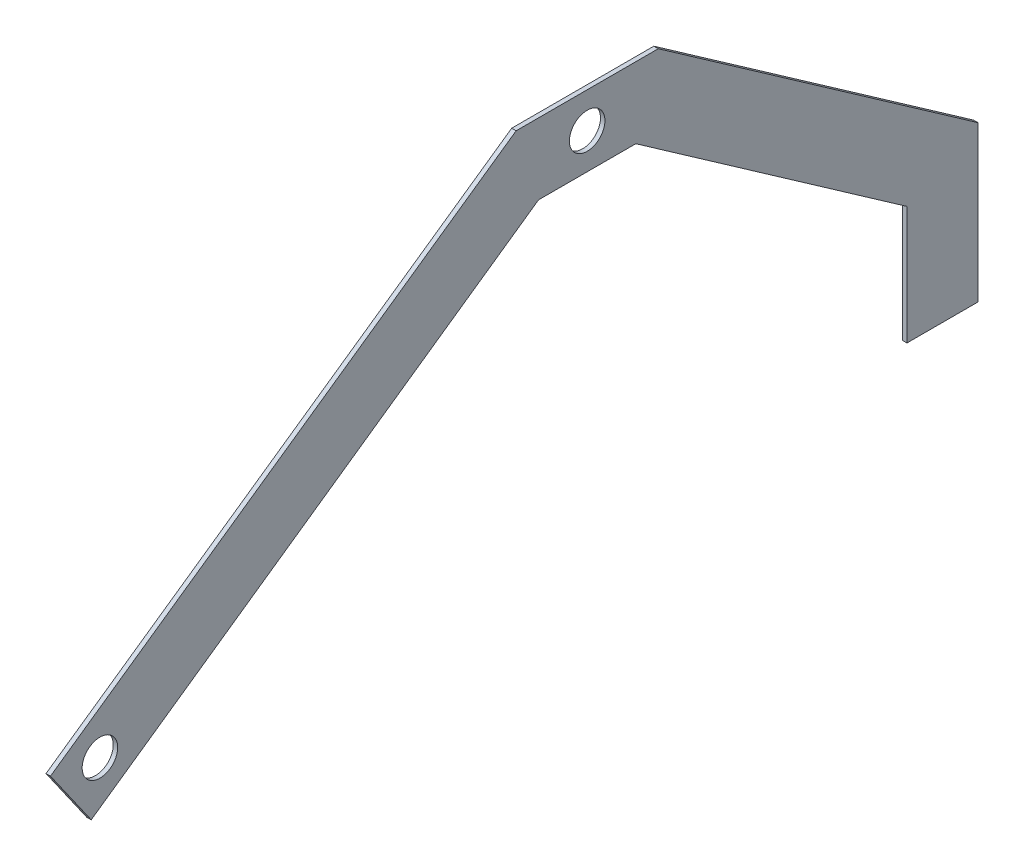
SolidWorks part; units mm, degrees
material "6063-O"
ref_plane "Front" through (0, 0, 0) normal (0, 0, 1) x (1, 0, 0)
ref_plane "Top" through (0, 0, 0) normal (0, 1, 0) x (1, 0, 0)
ref_plane "Right" through (0, 0, 0) normal (1, 0, 0) x (0, 0, -1)
sketch "Sketch1" plane through (0, 0, 0) normal (1, 0, 0) x (0, 0, -1)
  line L0 (-50.8, 25.4) -> (50.8, 25.4)
  line L3 (228.6, -161.1122) -> (34.7828, -25.4)
  line L4 (34.7828, -25.4) -> (-34.7828, -25.4)
  line L5 (-34.7828, -25.4) -> (-354.5657, -249.3144)
  line L6 (-354.5657, -249.3144) -> (-383.7034, -207.7015)
  line L7 (-383.7034, -207.7015) -> (-50.8, 25.4)
  line L8 (0, 25.4) -> (0, -25.4) construction
  line L9 (-278.5961, -165.1122) -> (-41236.1091, -28843.8715) construction
  line L13 (518.6127, -213.9391) -> (-49481.3873, -213.9391) construction
  line L14 (-147.7421, -347.18) -> (49852.2579, -347.18) construction
  line L15 (279.4, -134.6674) -> (279.4, -493.3391)
  line L16 (279.4, -493.3391) -> (228.6, -493.3391)
  line L17 (228.6, -493.3391) -> (228.6, -161.1122)
  line L18 (50.8, 25.4) -> (279.4, -134.6674)
  circle A0 centre (-348.3281, -213.9391) radius 12.7
  circle A1 centre (0, 0) radius 12.7
  point P10 (0, 0)
  point P16 (-369.1345, -228.5079)
  point P24 (254, -493.3391)
  dimension "D8" = 25.4
  dimension "D1" = 50.8
  dimension "D2" = 50.8
  dimension "D3" = 254
  dimension "D4" = 279.4
  dimension "D5" = 406.4
  dimension "D6" = 145
  dimension "D7" = 101.6
  dimension "D9" = 25.4
  dimension "D10" = 50.8
  dimension "D11" = 347.18
  dimension "D13" = 50.8
extrude "Boss-Extrude1" add sketch "Sketch1" along normal blind 3.175
sketch "Sketch3" plane through (3.175, 0, 0) normal (1, 0, 0) x (0, 0, -1)
  line L0 (254, -493.3391) -> (254, -116.8822) construction
  line L1 (228.6, -493.3391) -> (279.4, -493.3391) construction
  line L2 (279.4, -134.6674) -> (50.8, 25.4) construction
  circle A0 centre (254, -467.9391) radius 12.7
  dimension "D1" = 25.4
  dimension "D2" = 25.4
extrude "Cut-Extrude2" cut sketch "Sketch3" against normal through all
sketch "Sketch5" plane through (3.175, 0, 0) normal (1, 0, 0) x (0, 0, -1)
  line L0 (279.4, -493.3391) -> (279.4, -134.6674) construction
  line L1 (228.6, -493.3391) -> (279.4, -493.3391)
  line L2 (228.6, -493.3391) -> (228.6, -245.6891)
  line L3 (228.6, -245.6891) -> (279.4, -245.6891)
  line L4 (279.4, -493.3391) -> (279.4, -245.6891)
  dimension "D1" = 247.65
extrude "Cut-Extrude4" cut sketch "Sketch5" against normal through all
